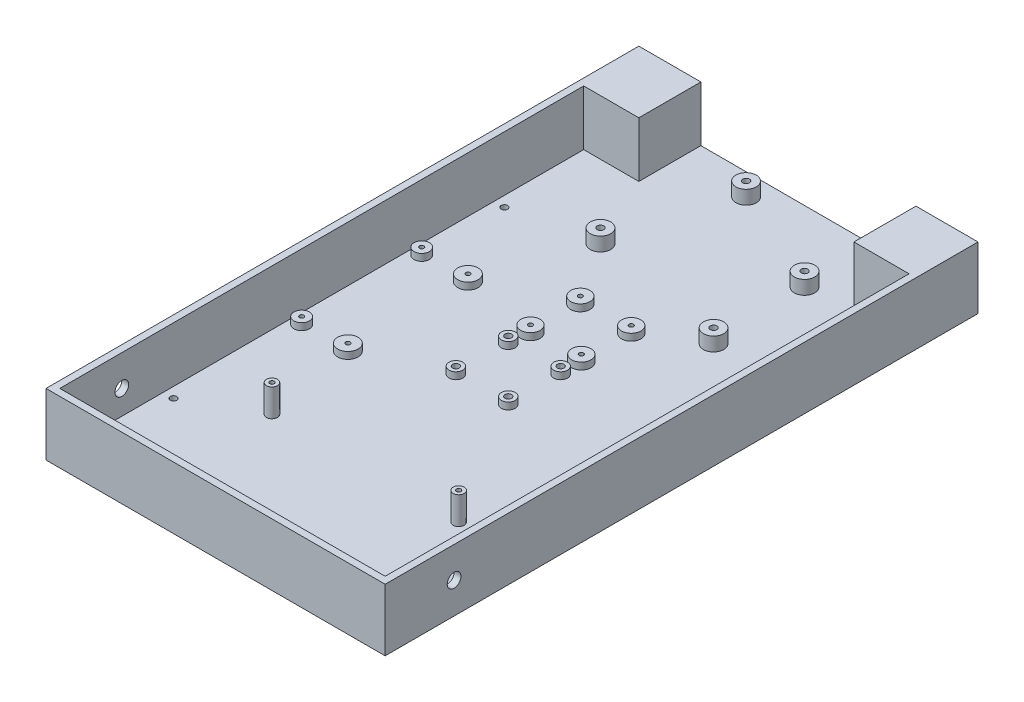
SolidWorks part; units mm, degrees
ref_plane "Front Plane" through (0, 0, 0) normal (0, 0, 1) x (1, 0, 0)
ref_plane "Top Plane" through (0, 0, 0) normal (0, 1, 0) x (1, 0, 0)
ref_plane "Right Plane" through (0, 0, 0) normal (1, 0, 0) x (0, 0, -1)
sketch "Sketch2" plane through (0, 0, 0) normal (0, 1, 0) x (1, 0, 0)
  line L0 (-61.1017, 40.0532) -> (88.7583, 40.0532)
  line L2 (88.7583, -232.9968) -> (-61.1017, -232.9968)
  line L4 (-61.1017, 40.0532) -> (-64.2767, 40.0532)
  line L5 (88.7583, 40.0532) -> (91.9333, 40.0532)
  line L6 (-64.2767, 40.0532) -> (-64.2767, -232.9968)
  line L7 (-64.2767, -232.9968) -> (-61.1017, -232.9968)
  line L8 (88.7583, -232.9968) -> (91.9333, -232.9968)
  line L9 (91.9333, -232.9968) -> (91.9333, 40.0532)
  circle A0 centre (-56.3392, -182.1968) radius 1.4986
  circle A1 centre (83.9958, -182.1968) radius 1.4986
  circle A2 centre (-56.3392, -29.7968) radius 1.4986
  circle A3 centre (83.9958, -29.7968) radius 1.4986
extrude "Boss-Extrude3" add sketch "Sketch2" along normal blind 3.175 contours L2 L7 L6 L4 L0 L5 L9 L8 | A1 | A0 | A2 | A3
sketch "Sketch7" plane through (0, 3.175, 0) normal (0, 1, 0) x (1, 0, 0)
  line L0 (-35.7017, 40.0532) -> (-64.2767, 40.0532)
  line L2 (-35.7017, 36.8782) -> (-35.7017, 40.0532)
  line L4 (63.3583, 36.8782) -> (63.3583, 40.0532)
  line L6 (-35.7017, 36.8782) -> (-61.1017, 36.8782)
  line L8 (-61.1017, 36.8782) -> (-61.1017, -229.8218)
  line L9 (-61.1017, -229.8218) -> (88.7583, -229.8218)
  line L10 (88.7583, -229.8218) -> (88.7583, 36.8782)
  line L11 (88.7583, 36.8782) -> (63.3583, 36.8782)
  line L12 (-64.2767, 40.0532) -> (-64.2767, -232.9968)
  line L13 (-64.2767, -232.9968) -> (91.9333, -232.9968)
  line L14 (91.9333, -232.9968) -> (91.9333, 40.0532)
  line L15 (91.9333, 40.0532) -> (63.3583, 40.0532)
extrude "Boss-Extrude4" add sketch "Sketch7" along normal blind 25.4
sketch "Sketch8" plane through (0, 3.175, 0) normal (0, 1, 0) x (1, 0, 0)
  circle A0 centre (-4.8407, 30.0202) radius 1.524
  circle A1 centre (-4.8407, 30.0202) radius 4.699
  circle A2 centre (-19.6997, -22.1768) radius 1.524
  circle A3 centre (44.5623, 7.5412) radius 1.524
  circle A4 centre (46.2133, -36.0198) radius 1.524
  circle A5 centre (-19.6997, -22.1768) radius 4.699
  circle A7 centre (44.5623, 7.5412) radius 4.699
  circle A8 centre (46.2133, -36.0198) radius 4.699
extrude "Boss-Extrude5" add sketch "Sketch8" along normal blind 6.35
extrude "Cut-Extrude1" cut sketch "Sketch8<3>" against normal through all contours A0 | A3 | A2 | A4 region at (-4.8407, 3.175, -30.0202) region at (-19.6997, 3.175, 22.1768) region at (44.5623, 3.175, -7.5412) region at (46.2133, 3.175, 36.0198)
sketch "Sketch8<3>" plane through (0, 3.175, 0) normal (0, 1, 0) x (1, 0, 0) same geometry as "Sketch8"
sketch "Sketch10" plane through (0, 3.175, 0) normal (0, 1, 0) x (1, 0, 0)
  circle A0 centre (-56.3392, -67.8968) radius 1.016
  circle A1 centre (-56.3392, -67.8968) radius 3.556
  circle A2 centre (-35.0413, -67.8968) radius 1.016
  circle A3 centre (-35.0413, -123.1926) radius 1.016
  circle A4 centre (-56.3392, -123.1926) radius 1.016
  circle A5 centre (-0.2924, -50.8644) radius 1.016
  circle A6 centre (23.1518, -50.8644) radius 1.016
  circle A7 centre (-0.2924, -73.8514) radius 1.016
  circle A8 centre (23.1518, -73.8514) radius 1.016
  circle A9 centre (-35.0413, -67.8968) radius 4.699
  circle A10 centre (-56.3392, -123.1926) radius 3.556
  circle A11 centre (-35.0413, -123.1926) radius 4.699
  circle A12 centre (-0.2924, -50.8644) radius 4.445
  circle A13 centre (23.1518, -50.8644) radius 4.445
  circle A14 centre (23.1518, -73.8514) radius 4.445
  circle A15 centre (-0.2924, -73.8514) radius 4.445
extrude "Boss-Extrude6" add sketch "Sketch10" along normal blind 3.175
extrude "Cut-Extrude2" cut sketch "Sketch10<2>" against normal through all contours A0 | A2 | A5 | A6 | A8 | A7 | A3 | A4
sketch "Sketch10<2>" plane through (0, 3.175, 0) normal (0, 1, 0) x (1, 0, 0) same geometry as "Sketch10"
sketch "Sketch11" plane through (0, 3.175, 0) normal (0, 1, 0) x (1, 0, 0)
  circle A0 centre (-27.288, -223.802) radius 1.016
  circle A1 centre (-27.3115, -165.89) radius 1.016
  circle A2 centre (58.691, -165.89) radius 1.016
  circle A3 centre (58.691, -223.802) radius 1.016
  circle A4 centre (-27.288, -223.802) radius 2.54
  circle A5 centre (-27.3115, -165.89) radius 2.54
  circle A6 centre (58.691, -165.89) radius 2.54
  circle A7 centre (58.691, -223.802) radius 2.54
extrude "Boss-Extrude7" add sketch "Sketch11" along normal blind 12.7
extrude "Cut-Extrude3" cut sketch "Sketch11<2>" against normal through all contours A1 | A2 | A3 | A0 region at (-27.288, 3.175, 223.802) region at (-27.3115, 3.175, 165.89) region at (58.691, 3.175, 165.89) region at (58.691, 3.175, 223.802)
sketch "Sketch11<2>" plane through (0, 3.175, 0) normal (0, 1, 0) x (1, 0, 0) same geometry as "Sketch11"
sketch "Sketch12" plane through (0, 3.175, 0) normal (0, 1, 0) x (1, 0, 0)
  line L6 (88.7583, 11.4782) -> (63.3583, 11.4782)
  line L7 (88.7583, -229.8218) -> (88.7583, 36.8782) construction
  line L12 (-35.7017, 36.8782) -> (-35.7017, 11.4782)
  line L15 (-35.7017, 11.4782) -> (-61.1017, 11.4782)
  line L16 (-61.1017, -229.8218) -> (-61.1017, 36.8782) construction
  line L17 (-61.1017, 11.4782) -> (-61.1017, 36.8782)
  line L18 (-61.1017, 36.8782) -> (-35.7017, 36.8782)
  line L19 (63.3583, 11.4782) -> (63.3583, 36.8782)
  line L20 (63.3583, 36.8782) -> (88.7583, 36.8782)
  line L21 (88.7583, 36.8782) -> (88.7583, 11.4782)
extrude "Boss-Extrude8" add sketch "Sketch12" along normal blind 25.4
sketch "Sketch13" plane through (-64.2767, 0, 0) normal (-1, 0, 0) x (0, 0, 1)
  circle A0 centre (201.2468, 14.2875) radius 3.175
extrude "Cut-Extrude4" cut sketch "Sketch13" against normal through all
sketch "Sketch14" plane through (0, 3.175, 0) normal (0, 1, 0) x (1, 0, 0)
  circle A0 centre (-0.9782, -83.3764) radius 1.524
  circle A1 centre (23.1518, -83.3764) radius 1.524
  circle A2 centre (23.1518, -107.5064) radius 1.524
  circle A3 centre (-0.9782, -107.5064) radius 1.524
  circle A4 centre (-0.9782, -83.3764) radius 3.175
  circle A5 centre (-0.9782, -107.5064) radius 3.175
  circle A6 centre (23.1518, -83.3764) radius 3.175
  circle A7 centre (23.1518, -107.5064) radius 3.175
extrude "Boss-Extrude9" add sketch "Sketch14" along normal blind 3.175
sketch "Sketch16" plane through (0, 3.175, 0) normal (0, 1, 0) x (1, 0, 0)
  circle A0 centre (-0.9782, -83.3764) radius 1.524
  circle A1 centre (23.1518, -83.3764) radius 1.524
  circle A2 centre (23.1518, -107.5064) radius 1.524
  circle A3 centre (-0.9782, -107.5064) radius 1.524
extrude "Cut-Extrude5" cut sketch "Sketch16" against normal through all
